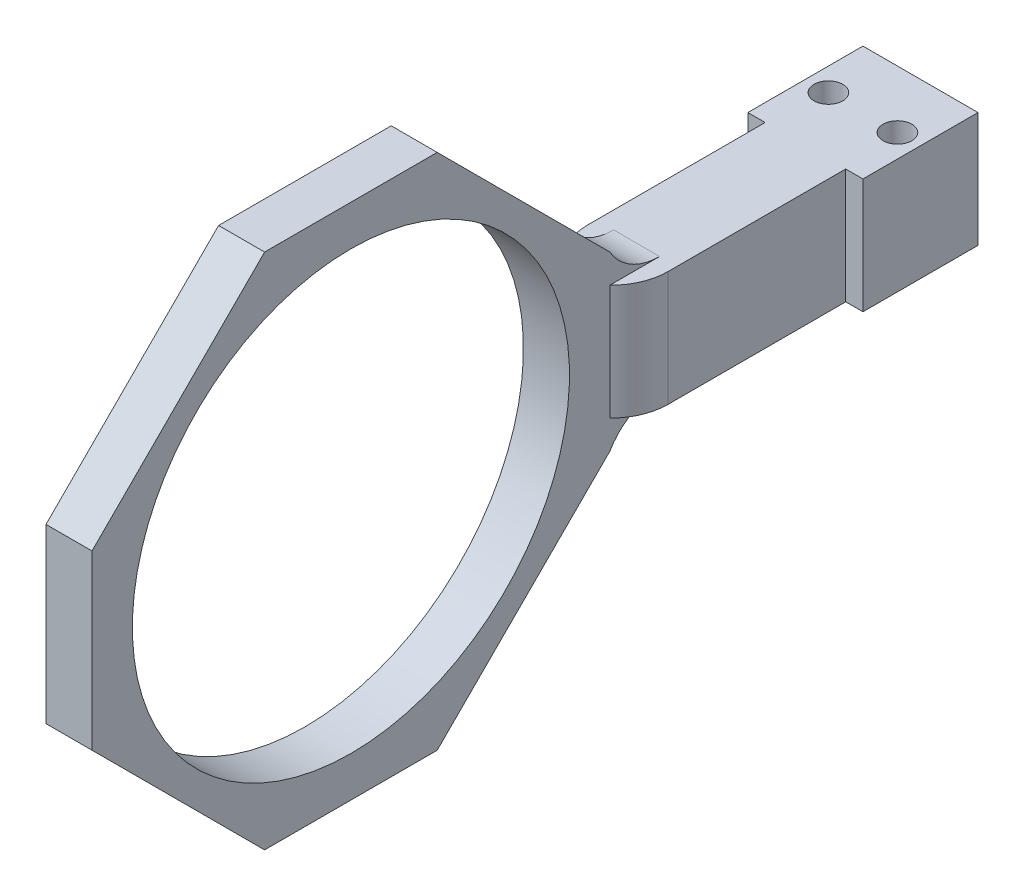
SolidWorks part; units mm, degrees
material "ABS"
ref_plane "前视基准面" through (0, 0, 0) normal (0, 0, 1) x (1, 0, 0)
ref_plane "上视基准面" through (0, 0, 0) normal (0, 1, 0) x (1, 0, 0)
ref_plane "右视基准面" through (0, 0, 0) normal (1, 0, 0) x (0, 0, -1)
other "Configuration Table"
sketch "草图1" plane through (0, 0, 0) normal (0, 0, 1) x (1, 0, 0)
  line L1 (-10, 10) -> (10, 10)
  line L2 (-10, 10) -> (-10, -10)
  line L3 (-10, -10) -> (10, -10)
  line L4 (10, 10) -> (10, -10)
  line L5 (-10, 10) -> (10, -10) construction
  line L6 (-10, -10) -> (10, 10) construction
  point P0 (0, 0)
  dimension "D1" = 20
  dimension "D2" = 20
extrude "凸台-拉伸1" add sketch "草图1" along normal blind 20
sketch "草图2" plane through (0, 0, 20) normal (0, 0, 1) x (1, 0, 0)
  line L0 (0, 10) -> (0, -10) construction
  line L1 (10, 10) -> (-10, 10) construction
  line L2 (-10, -10) -> (10, -10) construction
  line L4 (-7, 10) -> (7, 10)
  line L5 (-7, 10) -> (-7, -10)
  line L6 (-7, -10) -> (7, -10)
  line L7 (7, 10) -> (7, -10)
  line L8 (-7, 10) -> (7, -10) construction
  line L9 (-7, -10) -> (7, 10) construction
  point P6 (0, 0)
  dimension "D1" = 14
extrude "凸台-拉伸2" add sketch "草图2" along normal blind 38
sketch "草图8" plane through (0, 0, 58) normal (0, 0, 1) x (1, 0, 0)
  line L1 (4, 45) -> (-4, 45)
  line L2 (4, 45) -> (4, -45)
  line L3 (4, -45) -> (-4, -45)
  line L4 (-4, 45) -> (-4, -45)
  line L5 (4, 45) -> (-4, -45) construction
  line L6 (4, -45) -> (-4, 45) construction
  point P0 (0, 0)
  dimension "D1" = 90
  dimension "D2" = 8
extrude "凸台-拉伸4" add sketch "草图8" along normal blind 90
chamfer "倒角2" distance 30 angle 45 4 edges at (0, -45, 58) (0, 45, 58) (0, 45, 148) (0, -45, 148)
sketch "草图9" plane through (4, 0, 0) normal (1, 0, 0) x (0, 0, -1)
  line L0 (-103, 45) -> (-103, -45)
  line L1 (-118, 45) -> (-88, 45) construction
  line L2 (-118, -45) -> (-88, -45) construction
  circle A0 centre (-103, 0) radius 37.9894
extrude "切除-拉伸3" cut sketch "草图9" against normal blind 90 contours L0 A0 | L0 A0 region at (4, 0, 86.8768) region at (4, 0, 119.1232)
fillet "圆角1" radius 10 4 edges at (0, -10, 58) (0, 10, 58) (7, 0, 58) (-7, 0, 58)
sketch "草图10" plane through (0, 10, 0) normal (0, 1, 0) x (1, 0, 0)
  line L0 (-10, -10) -> (10, -10) construction
  line L1 (-10, -20) -> (-10, 0) construction
  line L2 (10, -20) -> (10, 0) construction
  line L3 (0, 0) -> (0, -37.3099) construction
  circle A0 centre (-6, -10) radius 2.5
  circle A1 centre (6, -10) radius 2.5
  point P10 (5.9338, -10)
  dimension "D2" = 5
  dimension "D3" = 5
  dimension "D1" = 12
  dimension "D4" = 4
extrude "切除-拉伸4" cut sketch "草图10" against normal blind 90
